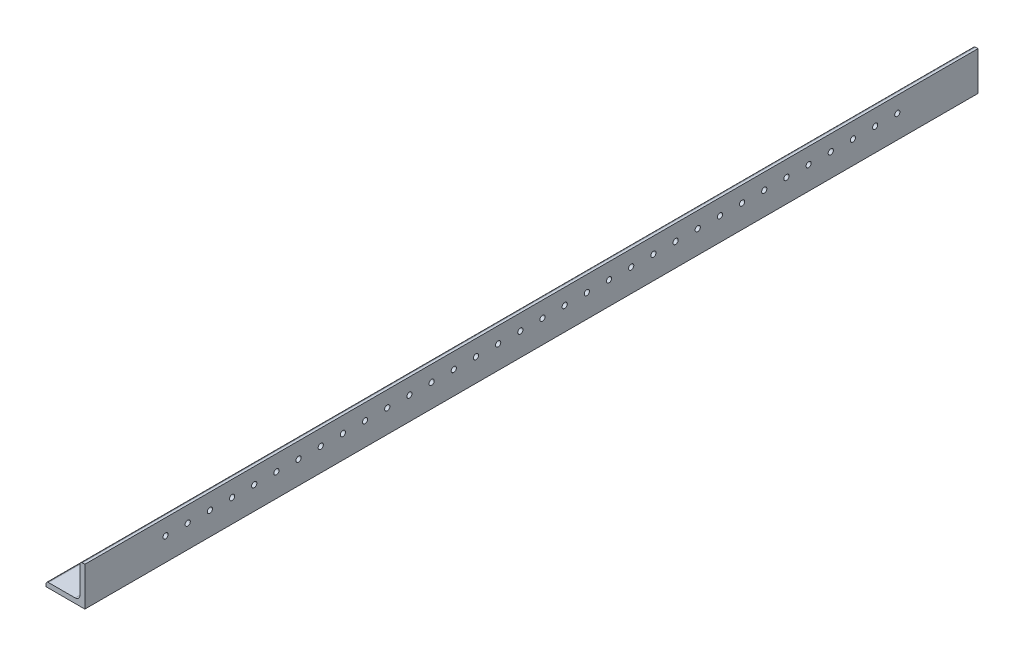
SolidWorks part; units mm, degrees
ref_plane "Front Plane" through (0, 0, 0) normal (0, 0, 1) x (1, 0, 0)
ref_plane "Top Plane" through (0, 0, 0) normal (0, 1, 0) x (1, 0, 0)
ref_plane "Right Plane" through (0, 0, 0) normal (1, 0, 0) x (0, 0, -1)
sketch "Sketch0" plane through (0, 0, 0) normal (0, 0, 1) x (1, 0, 0)
  line L0 (-12.7, -12.7) -> (12.7, -12.7)
  line L1 (12.7, -12.7) -> (12.7, 12.7)
  line L2 (12.7, 0) -> (0, 0) construction
  line L3 (0, 0) -> (0, -12.7) construction
  line L4 (9.525, -6.35) -> (9.525, 12.7) construction
  line L5 (6.35, -9.525) -> (-12.7, -9.525) construction
  arc A0 (9.525, -6.35) -> (6.35, -9.525) centre (6.35, -6.35) cw
  point P3 (8.5951, -8.5951)
  dimension "Inside Corner Radius" = 3.175
  dimension "Outside Height" = 25.4
  dimension "Inside Height" = 22.225
  dimension "Inside Width" = 22.225
  dimension "Wall Thickness" = 3.175
  dimension "D1" = 3.175
  dimension "Outside Width" = 25.4
sketch "Sketch1" plane through (0, 0, 0) normal (1, 0, 0) x (0, 0, -1)
  line L0 (609.6, 0) -> (-609.6, 0)
  point P4 (0, 0)
  dimension "Length" = 1219.2
sketch "Sketch2" plane through (0, 0, 0) normal (0, 0, 1) x (1, 0, 0)
  line L0 (-12.7, -12.7) -> (12.7, -12.7)
  line L1 (12.7, -12.7) -> (12.7, 12.7)
  line L2 (12.7, 12.7) -> (9.525, 12.7) construction
  line L3 (9.525, 11.1125) -> (9.525, -6.35)
  line L4 (6.35, -9.525) -> (-11.1125, -9.525)
  line L5 (-12.7, -12.7) -> (-12.7, -9.525) construction
  line L6 (11.1125, 12.7) -> (12.7, 12.7)
  line L7 (-12.7, -11.1125) -> (-12.7, -12.7)
  line L8 (12.7, 0) -> (0, 0) construction
  line L9 (0, 0) -> (0, -12.7) construction
  arc A0 (9.525, 11.1125) -> (11.1125, 12.7) centre (11.1125, 11.1125) cw
  arc A1 (-12.7, -11.1125) -> (-11.1125, -9.525) centre (-11.1125, -11.1125) cw
  arc A2 (9.525, -6.35) -> (6.35, -9.525) centre (6.35, -6.35) cw
  dimension "Inside Radius" = 3.175
  dimension "Height" = 25.4
  dimension "Width" = 25.4
  dimension "Thickness" = 3.175
extrude "Boss-Extrude1" add sketch "Sketch2" along normal mid plane 1219.2
sketch "Break Locations" plane through (0, 0, 0) normal (1, 0, 0) x (0, 0, -1)
  line L0 (-583.692, 0) -> (583.692, 0)
  line L1 (-609.6, -12.7) -> (-609.6, 12.7) construction
  line L2 (609.6, -12.7) -> (609.6, 12.7) construction
  point P0 (-588.01, 0)
  point P1 (588.01, 0)
  point P10 (0, 0)
  point P11 (583.692, 0)
  point P13 (-583.692, 0)
  dimension "D1" = 21.59
  dimension "D2" = 21.59
  dimension "D3" = 25.908
sketch "Sketch3" plane through (12.7, 0, 0) normal (1, 0, 0) x (0, 0, -1)
  line L0 (-609.6, -12.7) -> (609.6, -12.7) construction
  line L1 (609.6, 12.7) -> (-25.6, 12.7)
  line L2 (609.6, 12.7) -> (609.6, -12.7)
  line L3 (609.6, -12.7) -> (-25.6, -12.7)
  line L4 (-25.6, 12.7) -> (-25.6, -12.7)
  line L5 (-609.6, -12.7) -> (-609.6, 12.7) construction
  dimension "D1" = 584
extrude "Cut-Extrude2" cut sketch "Sketch3" against normal blind 30.48
sketch "Sketch5" plane through (9.525, 0, 0) normal (-1, 0, 0) x (0, 0, 1)
  line L0 (562.77, 11.1125) -> (562.77, -6.35) construction
  line L1 (609.6, 11.1125) -> (25.6, 11.1125) construction
  line L3 (609.6, -6.35) -> (25.6, -6.35) construction
  line L4 (72.43, 11.1125) -> (72.43, -6.35) construction
  line L6 (72.43, 2.3812) -> (562.77, 2.3812) construction
  line L7 (78.35, 2.3812) -> (72.43, 2.3812)
  line L8 (556.85, 2.3812) -> (562.77, 2.3812)
  line L9 (72.43, 8.7325) -> (72.43, -3.9675) construction
  line L10 (562.77, 8.7325) -> (562.77, -3.9675) construction
  circle A0 centre (78.35, 2.3812) radius 1.7
  circle A1 centre (92.85, 2.3812) radius 1.7
  circle A2 centre (107.35, 2.3812) radius 1.7
  circle A3 centre (121.85, 2.3812) radius 1.7
  circle A4 centre (136.35, 2.3812) radius 1.7
  circle A5 centre (150.85, 2.3812) radius 1.7
  circle A6 centre (165.35, 2.3812) radius 1.7
  circle A7 centre (179.85, 2.3812) radius 1.7
  circle A8 centre (194.35, 2.3812) radius 1.7
  circle A9 centre (208.85, 2.3812) radius 1.7
  circle A10 centre (223.35, 2.3812) radius 1.7
  circle A11 centre (237.85, 2.3812) radius 1.7
  circle A12 centre (252.35, 2.3812) radius 1.7
  circle A13 centre (266.85, 2.3812) radius 1.7
  circle A14 centre (281.35, 2.3812) radius 1.7
  circle A15 centre (295.85, 2.3812) radius 1.7
  circle A16 centre (310.35, 2.3812) radius 1.7
  circle A17 centre (324.85, 2.3812) radius 1.7
  circle A18 centre (339.35, 2.3812) radius 1.7
  circle A19 centre (353.85, 2.3812) radius 1.7
  circle A20 centre (368.35, 2.3812) radius 1.7
  circle A21 centre (382.85, 2.3812) radius 1.7
  circle A22 centre (397.35, 2.3812) radius 1.7
  circle A23 centre (411.85, 2.3812) radius 1.7
  circle A24 centre (426.35, 2.3812) radius 1.7
  circle A25 centre (440.85, 2.3812) radius 1.7
  circle A26 centre (455.35, 2.3812) radius 1.7
  circle A27 centre (469.85, 2.3812) radius 1.7
  circle A28 centre (484.35, 2.3812) radius 1.7
  circle A29 centre (498.85, 2.3812) radius 1.7
  circle A30 centre (513.35, 2.3812) radius 1.7
  circle A31 centre (527.85, 2.3812) radius 1.7
  circle A32 centre (542.35, 2.3812) radius 1.7
  circle A33 centre (556.85, 2.3812) radius 1.7
  dimension "D1" = 3.4
  dimension "D3" = 14.5
  dimension "D2" = 34
extrude "Cut-Extrude3" cut sketch "Sketch5" against normal through all contours A29 | A28 | A27 | A26 | A25 | A24 | A23 | A22 | A21 | A20 | A19 | A18 | A17 | A16 | A15 | A14 | A13 | A12 | A11 | A10 | A9 | A8 | A7 | A6 | A5 | A3 | A2 | A0 | A4 | A1 | A30 | A31 | A32 | A33 region at (9.525, 0.7293, 78.35) region at (9.525, 2.3812, 107.35) region at (9.525, 2.3812, 121.85) region at (9.525, 2.3812, 150.85) region at (9.525, 2.3812, 165.35) region at (9.525, 2.3812, 179.85) region at (9.525, 2.3812, 194.35) region at (9.525, 2.3812, 208.85) region at (9.525, 2.3812, 223.35) region at (9.525, 2.3812, 237.85) region at (9.525, 2.3812, 252.35) region at (9.525, 2.3812, 266.85) region at (9.525, 2.3812, 281.35) region at (9.525, 2.3812, 295.85) region at (9.525, 2.3812, 310.35) region at (9.525, 2.3812, 324.85) region at (9.525, 2.3812, 339.35) region at (9.525, 2.3812, 353.85) region at (9.525, 2.3812, 368.35) region at (9.525, 2.3812, 382.85) region at (9.525, 2.3812, 397.35) region at (9.525, 2.3812, 411.85) region at (9.525, 2.3812, 426.35) region at (9.525, 2.3812, 440.85) region at (9.525, 2.3812, 455.35) region at (9.525, 2.3812, 469.85) region at (9.525, 2.3812, 484.35) region at (9.525, 2.3812, 498.85)
sketch "Sketch7" plane through (0, -9.525, 0) normal (0, 1, 0) x (1, 0, 0)
  line L0 (-11.1125, -562.7675) -> (6.35, -562.7675) construction
  line L1 (-11.1125, -609.6) -> (-11.1125, -25.6) construction
  line L2 (-2.3812, -556.85) -> (-2.3812, -562.7675)
  line L3 (6.35, -609.6) -> (6.35, -25.6) construction
  line L5 (-2.3812, -72.4325) -> (-2.3812, -562.7675) construction
  line L6 (-2.3812, -78.35) -> (-2.3812, -72.4325)
  line L8 (-8.7325, -562.7675) -> (3.9675, -562.7675) construction
  line L9 (3.9675, -72.4325) -> (-8.7325, -72.4325) construction
  circle A0 centre (-2.3812, -78.35) radius 1.7
  circle A1 centre (-2.3812, -92.85) radius 1.7
  circle A2 centre (-2.3812, -107.35) radius 1.7
  circle A3 centre (-2.3812, -121.85) radius 1.7
  circle A4 centre (-2.3812, -136.35) radius 1.7
  circle A5 centre (-2.3812, -150.85) radius 1.7
  circle A6 centre (-2.3812, -165.35) radius 1.7
  circle A7 centre (-2.3812, -179.85) radius 1.7
  circle A8 centre (-2.3812, -194.35) radius 1.7
  circle A9 centre (-2.3812, -208.85) radius 1.7
  circle A10 centre (-2.3812, -223.35) radius 1.7
  circle A11 centre (-2.3812, -237.85) radius 1.7
  circle A12 centre (-2.3812, -252.35) radius 1.7
  circle A13 centre (-2.3812, -266.85) radius 1.7
  circle A14 centre (-2.3812, -281.35) radius 1.7
  circle A15 centre (-2.3812, -295.85) radius 1.7
  circle A16 centre (-2.3812, -310.35) radius 1.7
  circle A17 centre (-2.3812, -324.85) radius 1.7
  circle A18 centre (-2.3812, -339.35) radius 1.7
  circle A19 centre (-2.3812, -353.85) radius 1.7
  circle A20 centre (-2.3812, -368.35) radius 1.7
  circle A21 centre (-2.3812, -382.85) radius 1.7
  circle A22 centre (-2.3812, -397.35) radius 1.7
  circle A23 centre (-2.3812, -411.85) radius 1.7
  circle A24 centre (-2.3812, -426.35) radius 1.7
  circle A25 centre (-2.3812, -440.85) radius 1.7
  circle A26 centre (-2.3812, -455.35) radius 1.7
  circle A27 centre (-2.3812, -469.85) radius 1.7
  circle A28 centre (-2.3812, -484.35) radius 1.7
  circle A29 centre (-2.3812, -498.85) radius 1.7
  circle A30 centre (-2.3812, -513.35) radius 1.7
  circle A31 centre (-2.3812, -527.85) radius 1.7
  circle A32 centre (-2.3812, -542.35) radius 1.7
  circle A33 centre (-2.3812, -556.85) radius 1.7
  dimension "D2" = 3.4
  dimension "D3" = 14.5
  dimension "D1" = 34
extrude "Cut-Extrude4" cut sketch "Sketch7" against normal through all contours A0 | A1 | A2 | A3 | A4 | A5 | A6 | A7 | A8 | A9 | A10 | A11 | A12 | A13 | A14 | A15 | A16 | A17 | A18 | A19 | A20 | A21 | A22 | A23 | A24 | A25 | A26 | A27 | A28 | A29 | A23 | A30 | A31 | A33 | A32 region at (-3.5493, -9.525, 79.5181) region at (-2.3812, -9.525, 92.85) region at (-2.3812, -9.525, 107.35) region at (-2.3812, -9.525, 121.85) region at (-2.3812, -9.525, 136.35) region at (-2.3812, -9.525, 150.85) region at (-2.3812, -9.525, 165.35) region at (-2.3812, -9.525, 179.85) region at (-2.3812, -9.525, 194.35) region at (-2.3812, -9.525, 208.85) region at (-2.3812, -9.525, 223.35) region at (-2.3812, -9.525, 237.85) region at (-2.3812, -9.525, 252.35) region at (-2.3812, -9.525, 266.85) region at (-2.3812, -9.525, 281.35) region at (-2.3812, -9.525, 295.85) region at (-2.3812, -9.525, 310.35) region at (-2.3812, -9.525, 324.85) region at (-2.3812, -9.525, 339.35) region at (-2.3812, -9.525, 353.85) region at (-2.3812, -9.525, 368.35) region at (-2.3812, -9.525, 382.85) region at (-2.3812, -9.525, 397.35) region at (-2.3812, -9.525, 411.85) region at (-2.3812, -9.525, 426.35) region at (-2.3812, -9.525, 440.85) region at (-2.3812, -9.525, 455.35) region at (-2.3812, -9.525, 469.85) region at (-2.3812, -9.525, 484.35) region at (-2.3812, -9.525, 498.85)
equation "\"D1@Break Locations\" = .85 * \"Height@Sketch2\""
equation "\"D2@Break Locations\"=\"D1@Break Locations\""
equation "\"Thickness@Sketch2\" = \"Wall Thickness@Sketch0\""
equation "\"Height@Sketch2\" = \"Outside Height@Sketch0\""
equation "\"Width@Sketch2\" = \"Outside Width@Sketch0\""
equation "\"Inside Radius@Sketch2\" = \"Inside Corner Radius@Sketch0\""
equation "\"Length@Boss-Extrude1\" = \"Length@Sketch1\""
equation "\"D3@Break Locations\"=\"D2@Break Locations\"*1.2"
equation "\"D1@Sketch0\"=\"Wall Thickness@Sketch0\""
